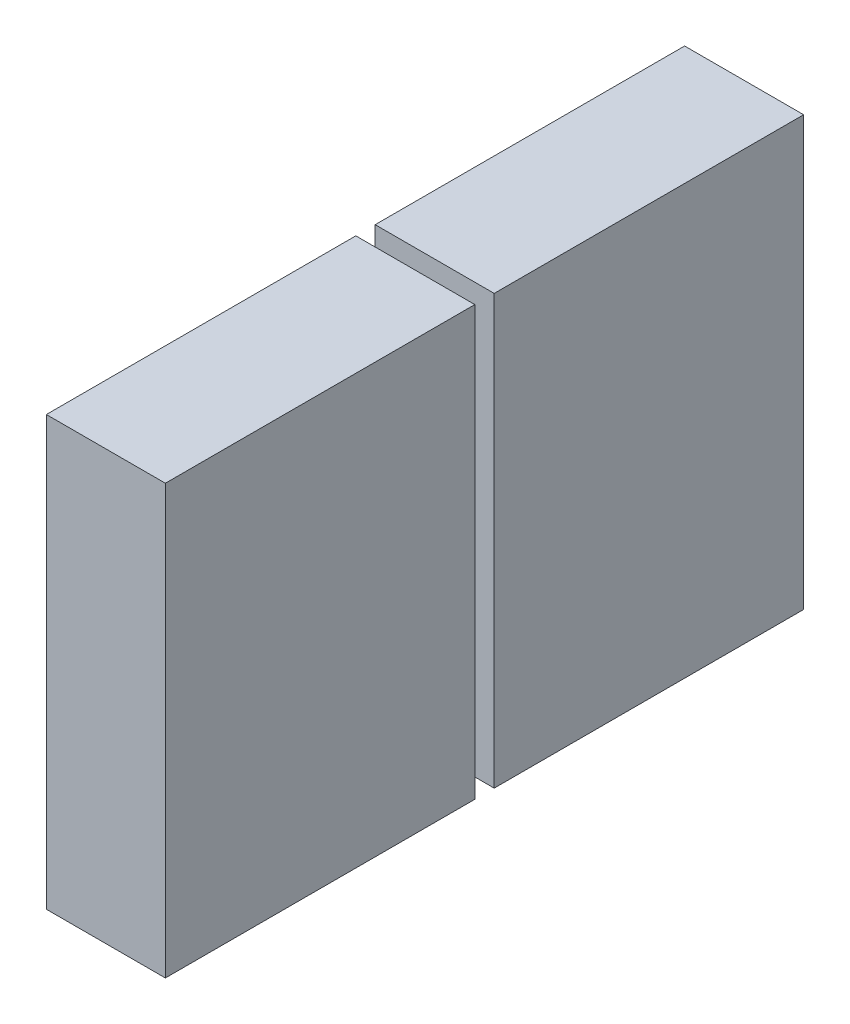
SolidWorks part; units mm, degrees
material "AISI 4130 Steel, normalized at 870C"
ref_plane "Front Plane" through (0, 0, 0) normal (0, 0, 1) x (1, 0, 0)
ref_plane "Top Plane" through (0, 0, 0) normal (0, 1, 0) x (1, 0, 0)
ref_plane "Right Plane" through (0, 0, 0) normal (1, 0, 0) x (0, 0, -1)
sketch "Sketch1" plane through (0, 0, 0) normal (0, 1, 0) x (1, 0, 0)
  line L0 (-825.5, 533.4) -> (-825.5, -533.4) construction
  line L1 (800.1, 533.4) -> (800.1, -533.4) construction
  line L2 (-1181.1, 177.8) -> (-1181.1, -177.8)
  line L3 (-1181.1, -177.8) -> (-546.1, -381)
  line L4 (-546.1, -381) -> (215.9, -431.8)
  line L6 (927.1, -203.2) -> (927.1, 203.2)
  line L8 (215.9, 431.8) -> (-546.1, 381)
  line L9 (-546.1, 381) -> (-1181.1, 177.8)
  line L10 (-2148.7043, 0) -> (1695.2305, 0) construction
  line L11 (-546.1, 381) -> (-546.1, -381) construction
  line L12 (215.9, 431.8) -> (215.9, -431.8) construction
  line L13 (927.1, 203.2) -> (215.9, 203.2)
  line L14 (927.1, -203.2) -> (215.9, -203.2)
  line L15 (215.9, 431.8) -> (368.3, 431.8)
  line L16 (215.9, -431.8) -> (368.3, -431.8)
  line L17 (215.9, 431.8) -> (215.9, 203.2)
  line L18 (215.9, -203.2) -> (215.9, -431.8)
  line L19 (-546.1, 381) -> (-546.1, -381)
  line L20 (215.9, 203.2) -> (215.9, -203.2)
  line L21 (-1181.1, 177.8) -> (-546.1, -381)
  line L22 (-546.1, 381) -> (-1181.1, -177.8)
  line L23 (-546.1, 0) -> (215.9, 0)
  line L24 (-38.1, 414.8667) -> (-38.1, -414.8667)
  line L25 (-292.1, 397.9333) -> (-292.1, -397.9333)
  line L26 (368.3, 431.8) -> (571.5, 203.2)
  line L27 (215.9, 203.2) -> (368.3, 431.8)
  line L28 (215.9, -203.2) -> (368.3, -431.8)
  line L29 (368.3, -431.8) -> (571.5, -203.2)
  line L30 (215.9, 203.2) -> (927.1, -203.2)
  point P14 (698.5, 0)
  point P18 (-825.5, -291.592)
  point P25 (-825.5, 291.592)
  point P31 (0, 0)
  point P32 (0, 0)
  dimension "D1" = 1066.8
  dimension "D2" = 1625.6
  dimension "D3" = 825.5
  dimension "D4" = 355.6
  dimension "D5" = 254
  dimension "2" = 635
  dimension "D6" = 762
  dimension "D7" = 863.6
  dimension "D8" = 406.4
  dimension "D9" = 711.2
  dimension "D10" = 762
  dimension "D11" = 355.6
  dimension "D12" = 254
  dimension "D13" = 152.4
sketch "Sketch2" plane through (0, 0, 0) normal (0, 1, 0) x (1, 0, 0)
  line L0 (-202148.7043, 0) -> (201695.2305, 0) construction
  line L1 (238.76, -10.16) -> (363.76, -10.16)
  line L2 (238.76, -10.16) -> (238.76, -335.16)
  line L3 (238.76, -335.16) -> (363.76, -335.16)
  line L4 (363.76, -10.16) -> (363.76, -335.16)
  line L5 (-202148.7043, 0) -> (201695.2305, 0) construction
  line L6 (215.9, 203.2) -> (215.9, -203.2) construction
  line L8 (238.76, 335.16) -> (363.76, 335.16)
  line L9 (238.76, 335.16) -> (238.76, 10.16)
  line L10 (238.76, 10.16) -> (363.76, 10.16)
  line L11 (363.76, 335.16) -> (363.76, 10.16)
  dimension "D1" = 125
  dimension "D2" = 325
  dimension "D3" = 22.86
  dimension "D4" = 125
  dimension "D5" = 325
  dimension "D6" = 20.32
sketch3d "3DSketch2"
  line L0 (-546.1, 0, 381) -> (-419.3813, 508, 389.4479)
  line L1 (-546.1, 0, -381) -> (-419.3813, 508, -389.4479)
  line L2 (-419.3813, 508, 389.4479) -> (-419.3813, 508, -389.4479)
  line L3 (-1181.1, 0, 177.8) -> (-1181.1, 304.8, 177.8)
  line L4 (-1181.1, 0, -177.8) -> (-1181.1, 304.8, -177.8)
  line L5 (-419.3813, 508, 389.4479) -> (-1181.1, 304.8, 177.8)
  line L6 (-419.3813, 508, -389.4479) -> (-1181.1, 304.8, -177.8)
  line L7 (-1181.1, 304.8, -177.8) -> (-1181.1, 304.8, 177.8)
  line L8 (-1181.1, 304.8, -177.8) -> (-1181.1, 0, 177.8)
  line L11 (-419.3813, 508, 389.4479) -> (-419.3813, 0, 389.4479) construction
  line L12 (-546.1, 0, 381) -> (215.9, 0, 431.8) construction
  dimension "D1" = 508
  dimension "D2" = 127
  dimension "D3" = 304.8
ref_plane "Plane1" through (215.9, 0, 0) normal (1, 0, 0) x (0, 0, -1)
sketch "Sketch4" plane through (215.9, 0, 0) normal (1, 0, 0) x (0, 0, -1)
  line L0 (-431.8, 0) -> (-431.8, 530.998)
  line L1 (0, 586.74) -> (0, -586.74) construction
  line L2 (-420.1842, 584.0592) -> (-115.3842, 1246.8612)
  line L3 (-431.8, 530.998) -> (431.8, 530.998)
  line L4 (420.1842, 584.0592) -> (115.3842, 1246.8612)
  line L5 (431.8, 0) -> (431.8, 530.998)
  arc A0 (115.3842, 1246.8612) -> (-115.3842, 1246.8612) centre (0, 1193.8) ccw
  arc A1 (-431.8, 530.998) -> (-420.1842, 584.0592) centre (-304.8, 530.998) cw
  arc A2 (431.8, 530.998) -> (420.1842, 584.0592) centre (304.8, 530.998) ccw
  point P0 (431.8, 0)
  point P2 (-431.8, 0)
  point P13 (-431.8, 558.8)
  dimension "D2" = 635
  dimension "D3" = 254
  dimension "D4" = 127
  dimension "D1" = 558.8
sketch3d "3DSketch4"
  line L0 (-466.9008, 317.5, -386.2799) -> (215.9, 254, -431.8)
  line L1 (-546.1, 0, -381) -> (-419.3813, 508, -389.4479) construction
  line L2 (215.9, 0, -431.8) -> (215.9, 530.998, -431.8) construction
  line L3 (215.9, 254, -431.8) -> (-546.1, 0, -381)
  line L5 (-466.9008, 317.5, -386.2799) -> (-466.9008, 0, -386.2799) construction
  line L7 (215.9, 0, -431.8) -> (-546.1, 0, -381) construction
  line L8 (-419.3813, 508, -389.4479) -> (-274.4866, 299.6056, -399.1076)
  line L9 (215.9, 254, 431.8) -> (-546.1, 0, 381)
  line L10 (-466.9008, 317.5, 386.2799) -> (215.9, 254, 431.8)
  line L11 (-419.3813, 508, 389.4479) -> (-274.4866, 299.6056, 399.1076)
  dimension "D1" = 317.5
  dimension "D3" = 254
  dimension "D2" = 254
sketch3d "3DSketch5"
  line L0 (-1181.1, 304.8, 177.8) -> (-546.1, 0, 381)
  line L1 (-1181.1, 304.8, 177.8) -> (-466.9008, 317.5, 386.2799)
  line L2 (-466.9008, 317.5, -386.2799) -> (-1181.1, 304.8, -177.8)
  line L3 (-546.1, 0, -381) -> (-1181.1, 304.8, -177.8)
sketch3d "3DSketch6"
  line L0 (927.1, 0, -203.2) -> (927.1, 381, -203.2)
  line L1 (927.1, 0, 203.2) -> (927.1, 381, 203.2)
  line L2 (927.1, 381, 203.2) -> (927.1, 381, -203.2)
  line L3 (571.5, 0, 203.2) -> (571.5, 381, 203.2)
  line L4 (571.5, 0, 203.2) -> (927.1, 381, 203.2)
  line L5 (215.9, 254, 431.8) -> (571.5, 381, 203.2)
  line L6 (215.9, 254, -431.8) -> (571.5, 0, -203.2)
  line L7 (215.9, 1320.8, 0) -> (215.9, 1219.2, 0) construction
  line L8 (215.9, 1219.2, 128.1046) -> (927.1, 381, 203.2)
  line L11 (215.9, 1219.2, 128.1046) -> (215.9, 985.737, 128.1046) construction
  line L12 (215.9, 1219.2, -128.1046) -> (927.1, 381, -203.2)
  line L13 (215.9, 584.0592, 420.1842) -> (215.9, 1246.8612, 115.3842) construction
  line L14 (215.9, 1219.2, 128.1046) -> (215.9, 1219.2, 0) construction
  line L15 (571.5, 381, 203.2) -> (927.1, 381, 203.2)
  line L16 (215.9, 254, 431.8) -> (571.5, 0, 203.2)
  line L17 (571.5, 381, 203.2) -> (215.9, 530.998, 431.8)
  line L18 (215.9, 254, -431.8) -> (571.5, 381, -203.2)
  line L19 (571.5, 0, -203.2) -> (571.5, 381, -203.2)
  line L20 (571.5, 0, -203.2) -> (927.1, 381, -203.2)
  line L21 (571.5, 381, -203.2) -> (927.1, 381, -203.2)
  line L22 (927.1, 381, 203.2) -> (927.1, 0, -203.2)
  line L23 (571.5, 381, -203.2) -> (215.9, 530.998, -431.8)
  arc A0 (215.9, 1246.8612, -115.3842) -> (215.9, 1246.8612, 115.3842) centre (215.9, 1193.8, 0) ccw construction
  point P17 (342.9, 1193.8, 0)
  point P20 (215.9, 1066.8, 0)
  point P21 (215.9, 1066.8, 0)
  dimension "D1" = 381
  dimension "D2" = 101.6
extrude "Boss-Extrude1" add sketch "Sketch2" along normal blind 450
sketch "Sketch6" plane through (0, 0, 0) normal (0, 0, 1) x (1, 0, 0)
  line L0 (215.9, 1246.8612) -> (215.9, 1320.8) construction
  line L1 (215.9, 1246.8612) -> (215.9, 1320.8) construction
  line L2 (-1181.1, 304.8) -> (215.9, 1320.8)
  line L3 (76.2, 0) -> (76.2, 1016)
  line L4 (215.9, 0) -> (-546.1, 0) construction
  line L5 (215.9, 584.0592) -> (215.9, 1246.8612) construction
  point P10 (0, 0)
  dimension "D1" = 1016
  dimension "D2" = 139.7
